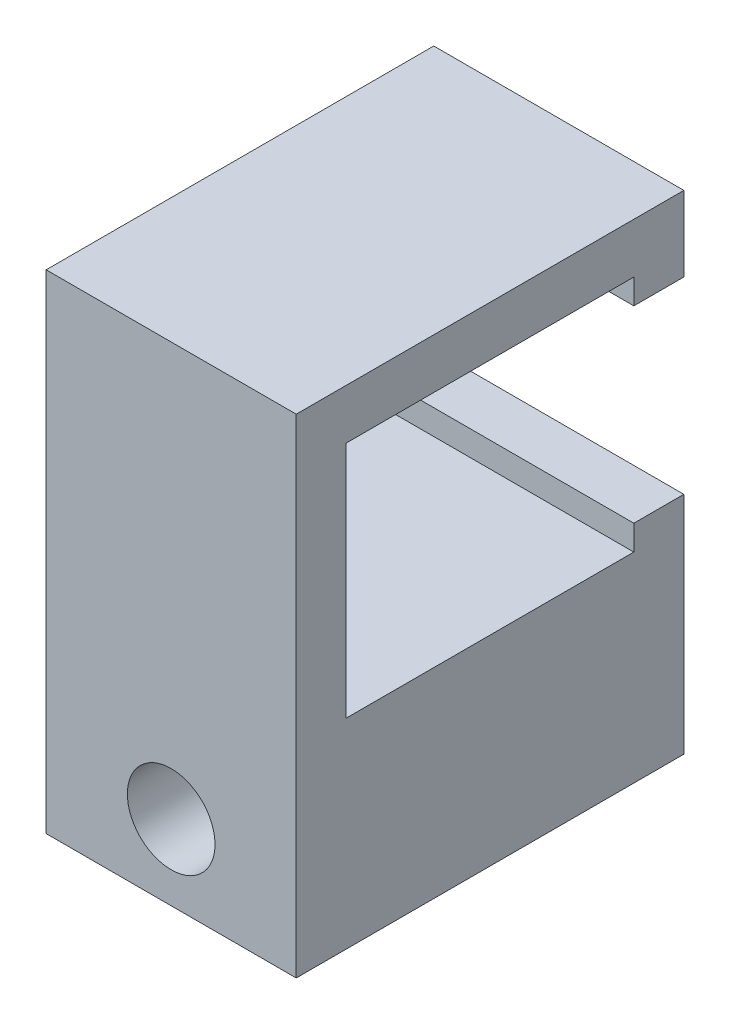
SolidWorks part; units mm, degrees
ref_plane "Front Plane" through (0, 0, 0) normal (0, 0, 1) x (1, 0, 0)
ref_plane "Top Plane" through (0, 0, 0) normal (0, 1, 0) x (1, 0, 0)
ref_plane "Right Plane" through (0, 0, 0) normal (1, 0, 0) x (0, 0, -1)
sketch "Sketch1" plane through (0, 0, 0) normal (1, 0, 0) x (0, 0, -1)
  line L5 (9.4948, 5.4238) -> (-6.0052, 5.4238)
  line L11 (-4.0052, -4.5137) -> (145.9948, -4.5137) construction
  line L12 (5.9948, 1.8363) -> (5.9948, -4.5137) construction
  line L15 (9.4948, 5.4238) -> (9.4948, 2.4238)
  line L16 (9.4948, 2.4238) -> (7.4948, 2.4238)
  line L17 (7.4948, 2.4238) -> (7.4948, 3.4238)
  line L18 (7.4948, 3.4238) -> (-4.0052, 3.4238)
  line L19 (-4.0052, 3.4238) -> (-4.0052, -6.1012)
  line L20 (-6.0052, 5.4238) -> (-6.0052, -8.1012)
  line L21 (7.4948, -6.1012) -> (-4.0052, -6.1012)
  line L22 (7.4948, -5.1012) -> (7.4948, -6.1012)
  line L23 (9.4948, -5.1012) -> (7.4948, -5.1012)
  line L25 (9.4948, -8.1012) -> (-6.0052, -8.1012)
  line L26 (9.4948, -5.1012) -> (9.4948, -8.1012)
  line L28 (-4.0052, 1.8363) -> (-4.0052, -4.5137) construction
  point P16 (-6.0052, -1.3387)
  point P17 (-4.0052, -1.3387)
  point P24 (-4.0052, -1.3387)
  dimension "D2" = 2
  dimension "D3" = 1
  dimension "D4" = 2
  dimension "D5" = 1.5
  dimension "D6" = 1.5875
  dimension "D1" = 2
extrude "MainBody" add sketch "Sketch1" along normal mid plane 10
sketch "Sketch4" plane through (0, -8.1012, 0) normal (0, -1, 0) x (1, 0, 0)
  line L4 (-5, 6.0052) -> (-5, -9.4948)
  line L5 (-5, -9.4948) -> (5, -9.4948)
  line L6 (5, -9.4948) -> (5, 6.0052)
  line L7 (5, 6.0052) -> (-5, 6.0052)
  line L8 (-5, 6.0052) -> (-5, -9.4948)
  line L9 (-5, -9.4948) -> (5, -9.4948)
  line L10 (5, -9.4948) -> (5, 6.0052)
  line L11 (5, 6.0052) -> (-5, 6.0052)
  dimension "D1" = 0
extrude "Boss-Extrude1" add sketch "Sketch4" along normal blind 6
hole_wizard "#6-32 Tapped Hole1" positions "Sketch2" profile "Sketch3" tap size "#6-32" standard "ANSI Inch" end condition through all
sketch "Sketch2" plane through (0, 0, 6.0052) normal (0, 0, 1) x (1, 0, 0)
  line L2 (5, -14.1012) -> (-5, -14.1012) construction
  point P0 (0, -11.1012)
  point P12 (0, -14.1012)
  dimension "D1" = 3
sketch "Sketch3" plane through (0, -11.1012, 6.0052) normal (1, 0, 0) x (0, -1, 0)
  line L0 (0, 0) -> (0, 15.5)
  line L1 (0, 15.5) -> (1.7526, 15.5)
  line L2 (1.7526, 15.5) -> (1.7526, 0)
  line L5 (1.7526, 0) -> (0, 0)
  line L11 (0, -6.35) -> (0, 107.95) construction
  dimension "Thread Major Dia." = 3.5052
  dimension "Thru Tap Drill Depth" = 15.5
equation "\"HeightBarThickness\"= 1.5875"
equation "\"HeightBarWidth\"=6"
equation "\"SheetThickness\"= 1.5875"
equation "\"D2@Sketch1\"=2mm"
equation "\"HeightBarTolerance\"= 0.1mm"
